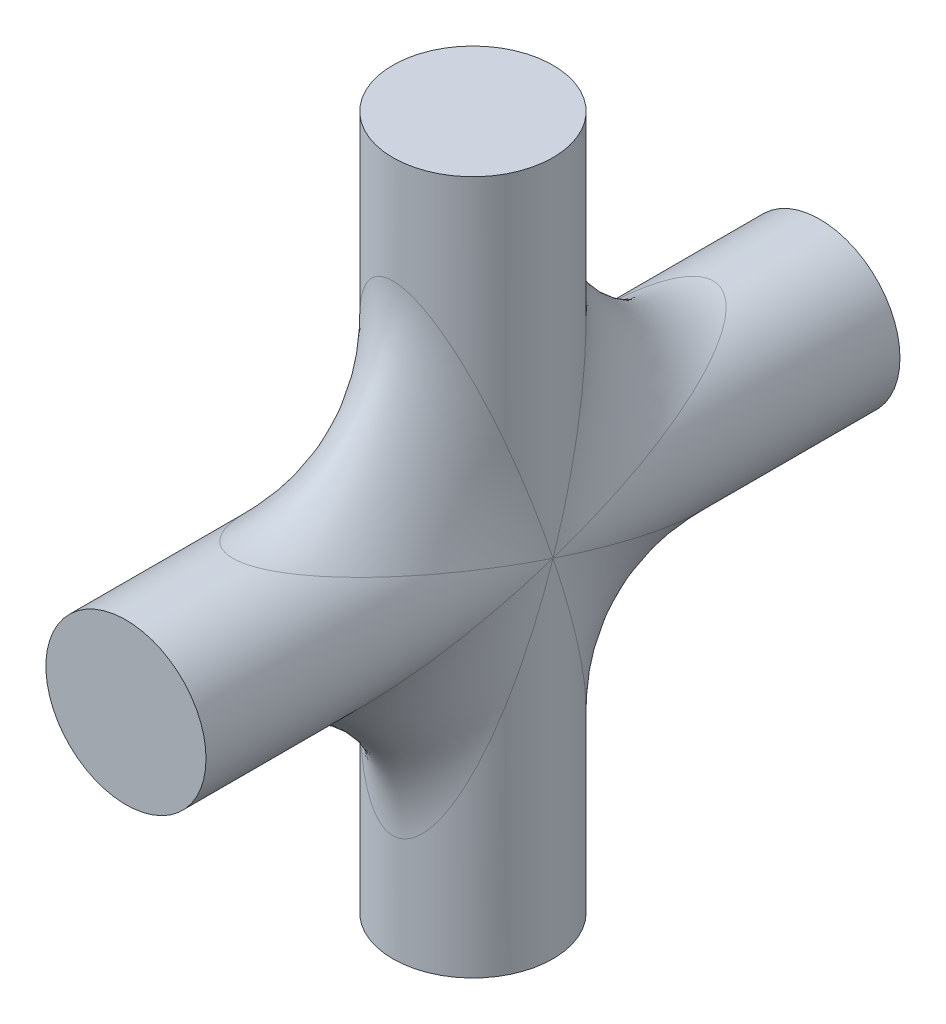
SolidWorks part; units mm, degrees
ref_plane "Front Plane" through (0, 0, 0) normal (0, 0, 1) x (1, 0, 0)
ref_plane "Top Plane" through (0, 0, 0) normal (0, 1, 0) x (1, 0, 0)
ref_plane "Right Plane" through (0, 0, 0) normal (1, 0, 0) x (0, 0, -1)
sketch "Sketch1" plane through (0, 0, 0) normal (0, 0, 1) x (1, 0, 0)
  circle A0 centre (0, 0) radius 4.7625
  dimension "D1" = 9.525
extrude "Boss-Extrude1" add sketch "Sketch1" along normal mid plane 41.275
sketch "Sketch2" plane through (0, 0, 0) normal (0, 1, 0) x (1, 0, 0)
  circle A0 centre (0, 0) radius 4.7625
extrude "Boss-Extrude2" add sketch "Sketch2" along normal mid plane 41.275
fillet "Fillet1" radius 9.525 4 edges at (0, 4.7625, 4.7625) (0, 4.7625, -4.7625) (0, -4.7625, -4.7625) (0, -4.7625, 4.7625)
scale "Scale1" scale about origin uniform scaling yes scale factor 0.35
